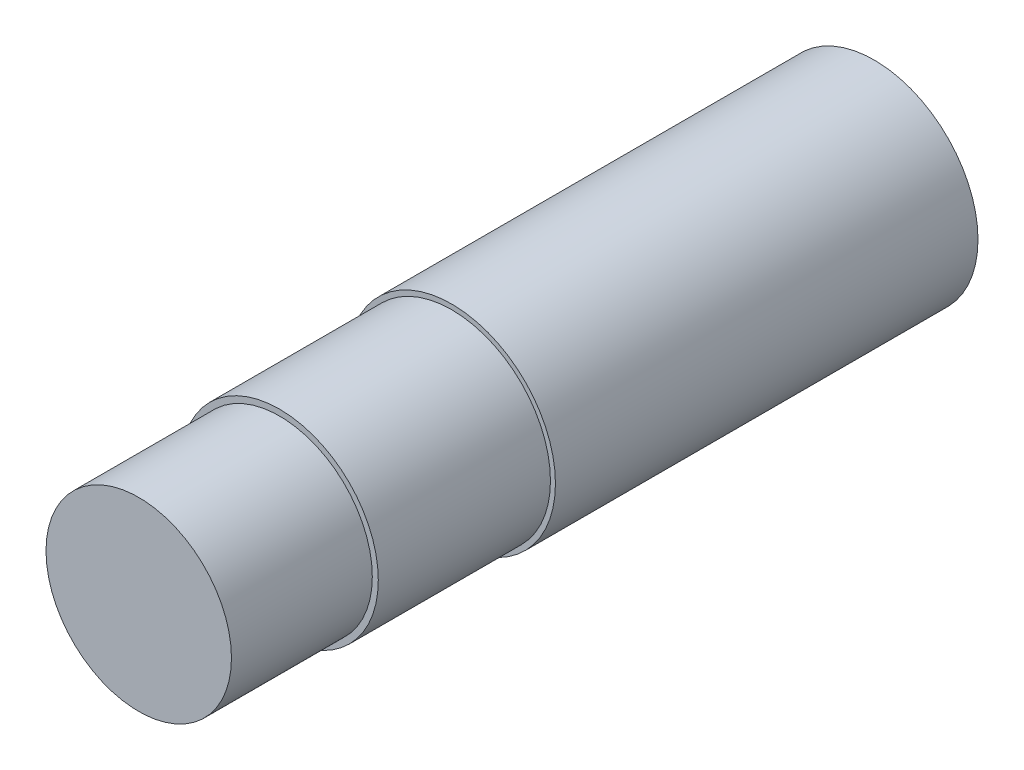
SolidWorks part; units mm, degrees
ref_plane "Front Plane" through (0, 0, 0) normal (0, 0, 1) x (1, 0, 0)
ref_plane "Top Plane" through (0, 0, 0) normal (0, 1, 0) x (1, 0, 0)
ref_plane "Right Plane" through (0, 0, 0) normal (1, 0, 0) x (0, 0, -1)
sketch "Sketch1" plane through (0, 0, 0) normal (0, 0, 1) x (1, 0, 0)
  circle A0 centre (0, 0) radius 6.625
  circle A1 centre (0, 0) radius 6.3072
  dimension "D1" = 13.25
extrude "Boss-Extrude1" add sketch "Sketch1" along normal blind 27 contours A1 | A0 A1 region at (-6.4376, 0, 0) region at (0, 0, 0)
extrude "Boss-Extrude2" add sketch "Sketch1<3>" along normal blind 38 contours A1 region at (0, 0, 0)
sketch "Sketch1<3>" plane through (0, 0, 0) normal (0, 0, 1) x (1, 0, 0) same geometry as "Sketch1"
sketch "Sketch2" plane through (0, 0, 38) normal (0, 0, 1) x (1, 0, 0)
  circle A0 centre (0, 0) radius 5.925
extrude "Boss-Extrude3" add sketch "Sketch2" along normal blind 9
